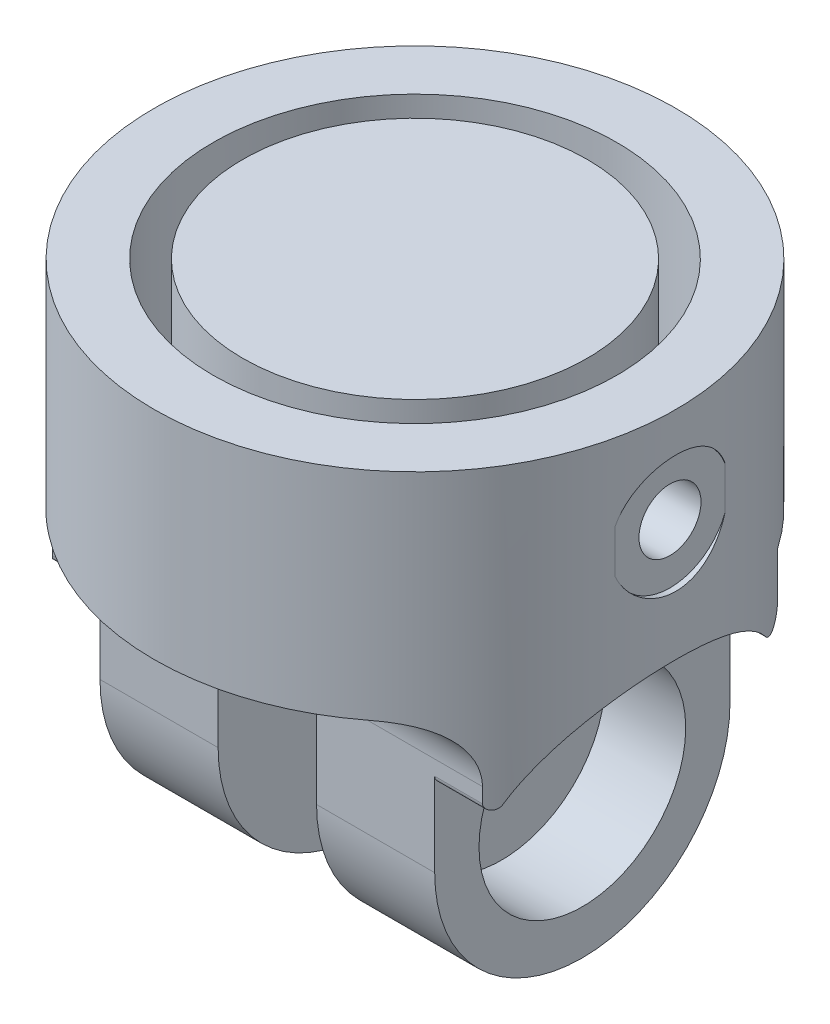
SolidWorks part; units mm, degrees
material "PLA Black"
ref_plane "Front" through (0, 0, 0) normal (0, 0, 1) x (1, 0, 0)
ref_plane "Top" through (0, 0, 0) normal (0, 1, 0) x (1, 0, 0)
ref_plane "Right" through (0, 0, 0) normal (1, 0, 0) x (0, 0, -1)
sketch "Sketch1" plane through (0, 0, 0) normal (0, 1, 0) x (1, 0, 0)
  line L0 (0, 8.75) -> (0, 10.25) construction
  circle A0 centre (0, 0) radius 10.25
  circle A1 centre (0, 0) radius 13.25
  circle A2 centre (0, 0) radius 9.5 construction
  circle A4 centre (0, 0) radius 8.75
  point P11 (0, 9.5)
  dimension "D1" = 1.5
  dimension "D2" = 3
  dimension "D3" = 19
extrude "Boss-Extrude1" add sketch "Sketch1" along normal blind 10 contours A1 A0 | A4 region at (-12.8752, 0, 0) region at (0, 0, 0)
sketch "Sketch3" plane through (0, 0, 0) normal (0, -1, 0) x (1, 0, 0)
  circle A2 centre (0, 0) radius 13.25 construction
  circle A3 centre (0, 0) radius 13.25
extrude "Boss-Extrude2" add sketch "Sketch3" along normal blind 1
sketch "Sketch4" plane through (0, -1, 0) normal (0, -1, 0) x (1, 0, 0)
  line L0 (0, 17.8908) -> (0, -17.0763) construction
  line L1 (2.5, 7.5) -> (8.5, 7.5)
  line L2 (2.5, 7.5) -> (2.5, -7.5)
  line L3 (2.5, -7.5) -> (8.5, -7.5)
  line L4 (8.5, 7.5) -> (8.5, -7.5)
  line L5 (-8.5, 7.5) -> (-8.5, -7.5)
  line L6 (-2.5, -7.5) -> (-8.5, -7.5)
  line L7 (-2.5, 7.5) -> (-2.5, -7.5)
  line L8 (-2.5, 7.5) -> (-8.5, 7.5)
  line L9 (16.8049, 0) -> (-19.8998, 0) construction
  dimension "D1" = 6
  dimension "D2" = 5
  dimension "D3" = 15
extrude "Boss-Extrude3" add sketch "Sketch4" along normal blind 16
sketch "Sketch5" plane through (8.5, 0, 0) normal (1, 0, 0) x (0, 0, -1)
  line L0 (-7.5, -17) -> (-7.5, -1) construction
  line L1 (7.5, -17) -> (7.5, -1) construction
  line L2 (7.5, -9) -> (7.5, -17.1619)
  line L3 (7.5, -17.1619) -> (-7.5, -17.1619)
  line L4 (-7.5, -17.1619) -> (-7.5, -9)
  arc A0 (-7.5, -9) -> (7.5, -9) centre (0, -9) ccw
  circle A1 centre (0, -9) radius 1.75
  dimension "D1" = 3.5
extrude "Cut-Extrude1" cut sketch "Sketch5" against normal through all both and the other way through all
sketch "Sketch6" plane through (8.5, 0, 0) normal (1, 0, 0) x (0, 0, -1)
  circle A0 centre (0, -9) radius 5.25
  dimension "D1" = 10.5
extrude "Cut-Extrude2" cut sketch "Sketch6" against normal blind 4.1
mirror "Mirror1" about plane through (0, 0, 0) normal (1, 0, 0) of "Cut-Extrude2"
ref_plane "Plane9" through (2.25, 0, 0) normal (1, 0, 0) x (0, 0, -1)
sketch "Sketch7" plane through (2.25, 0, 0) normal (1, 0, 0) x (0, 0, -1)
  line L0 (3.6, -9) -> (3.6, -1) construction
  line L1 (7.5, -1) -> (-7.5, -1) construction
  line L2 (3.5026, -8.1681) -> (1.8, -1) construction
  line L3 (3.2149, -7.38) -> (0, -1) construction
  line L4 (1.8, -0.6757) -> (1.8, -1.4422) construction
  line L5 (2.8087, -6.748) -> (-1.8, -1) construction
  line L6 (2.3875, -6.3056) -> (-3.6, -1) construction
  line L8 (0, -1.6788) -> (0, 0) construction
  line L9 (-8.4824, -9) -> (8.712, -9) construction
  line L10 (2.0173, -6.0183) -> (-5.4, -1) construction
  line L11 (-3.6, -0.3587) -> (-3.6, -1.6788) construction
  circle A0 centre (0, -9) radius 3.6 construction
  dimension "D1" = 7.2
  dimension "D2" = 34.081
  dimension "D3" = 8
ref_plane "Plane1" through (2.25, -1, -3.6) normal (0, 1, 0) x (1, 0, 0)
ref_plane "Plane2" through (2.25, -1, -1.8) normal (0, 0.9729, 0.2311) x (1, 0, 0)
ref_plane "Plane3" through (2.25, -1, 0) normal (0, 0.893, 0.45) x (1, 0, 0)
ref_plane "Plane5" through (2.25, -1, 1.8) normal (0, 0.7802, 0.6255) x (1, 0, 0)
ref_plane "Plane6" through (2.25, -1, 3.6) normal (0, 0.6632, 0.7484) x (1, 0, 0)
ref_plane "Plane7" through (2.25, -1, 5.4) normal (0, 0.5604, 0.8282) x (1, 0, 0)
sketch "Sketch8" plane through (2.25, -1, -3.6) normal (0, 1, 0) x (1, 0, 0)
  circle A0 centre (0, 0) radius 0.825
  dimension "D1" = 1.65
extrude "Cut-Extrude5" cut sketch "Sketch8" along normal blind 5.5 and the other way through all
sketch "Sketch9" plane through (2.25, -1, -1.8) normal (0, 0.9729, 0.2311) x (1, 0, 0)
  circle A0 centre (0, 0) radius 0.825
  dimension "D1" = 1.65
extrude "Cut-Extrude3" cut sketch "Sketch9" along normal blind 5.5
sketch "Sketch10" plane through (2.25, -1, 0) normal (0, 0.893, 0.45) x (1, 0, 0)
  circle A0 centre (0, 0) radius 0.825
  dimension "D1" = 1.65
sketch "Sketch11" plane through (2.25, -1, 1.8) normal (0, 0.7802, 0.6255) x (1, 0, 0)
  circle A0 centre (0, 0) radius 0.825
  dimension "D1" = 1.65
sketch "Sketch12" plane through (2.25, -1, 3.6) normal (0, 0.6632, 0.7484) x (1, 0, 0)
  circle A0 centre (0, 0) radius 0.825
  dimension "D1" = 1.65
sketch "Sketch14" plane through (2.25, -1, 5.4) normal (0, 0.5604, 0.8282) x (1, 0, 0)
  circle A0 centre (0, 0) radius 0.825
  dimension "D1" = 1.65
extrude "Cut-Extrude6" cut sketch "Sketch10" along normal blind 5.5 and the other way through all
extrude "Cut-Extrude7" cut sketch "Sketch11" along normal blind 5.5 and the other way through all contours A0
extrude "Cut-Extrude8" cut sketch "Sketch12" along normal blind 5.5 and the other way through all contours A0
extrude "Cut-Extrude9" cut sketch "Sketch14" along normal blind 5.5 and the other way through all contours A0
ref_plane "Plane8" through (13.25, 0, 0) normal (1, 0, 0) x (0, 0, -1)
hole_wizard "Tap Drill for M3 Helicoil1" positions "Sketch17" profile "Sketch18" hole size "M3x0.5" standard "DIN"
sketch "Sketch17" plane through (13.25, 0, 0) normal (1, 0, 0) x (0, 0, -1)
  line L0 (-22.2973, 5) -> (18.0703, 5) construction
  line L4 (0, 12.2732) -> (0, -5.3405) construction
  line L6 (-7.5, -9) -> (-7.5, -1) construction
  line L7 (7.5, -9) -> (7.5, -1) construction
  line L8 (13.25, 10) -> (-13.25, 10) construction
  line L9 (10.25, 0) -> (-10.25, 0) construction
  point P0 (0, 5)
sketch "Sketch18" plane through (13.25, 5, 0) normal (0, 1, 0) x (0, 0, -1)
  line L0 (0, 0) -> (0, 6.9464)
  line L1 (0, 6.9464) -> (1.575, 6)
  line L2 (1.575, 6) -> (1.575, 0)
  line L5 (1.575, 0) -> (0, 0)
  line L10 (0, 6.9464) -> (-1.575, 6) construction
  line L11 (0, -6.35) -> (0, 107.95) construction
  dimension "Hole Dia." = 3.15
  dimension "Hole Depth" = 6
  dimension "Drill Angle" = 118
sketch "Sketch20" plane through (13.25, 0, 0) normal (1, 0, 0) x (0, 0, -1)
  circle A0 centre (0, 5) radius 3
  dimension "D1" = 6
extrude "Cut-Extrude10" cut sketch "Sketch20" against normal blind 0.3
sketch "Sketch21" plane through (8.5, 0, 0) normal (1, 0, 0) x (0, 0, -1)
  line L0 (7.5, -1) -> (-7.5, -1) construction
  line L1 (7.5, -0.1252) -> (7.5, -3.188)
  line L2 (0.9244, -19.5662) -> (-4.8209, -14.7453) construction
  line L3 (0, 5.2718) -> (0, -9.2894) construction
  line L4 (0, 10) -> (0, -1) construction
  line L5 (-7.5, -0.1252) -> (-7.5, -4.7575)
  line L6 (7.5, -0.1252) -> (-7.5, -0.1252)
  line L7 (-7.5, -9) -> (-7.5, -1) construction
  line L8 (7.5, -9) -> (7.5, -1) construction
  line L9 (0, -1) -> (9.1102, -5.2607) construction
  line L10 (0, -1) -> (1.2641, -0.2702) construction
  line L11 (6.0277, -3.7401) -> (7.5, -3.188) construction
  line L12 (10.5662, -8.0756) -> (4.8209, -3.2547) construction
  line L13 (-4.8209, -14.7453) -> (4.8209, -3.2547) construction
  line L14 (10.5662, -8.0756) -> (0.9244, -19.5662) construction
  arc A0 (-6.8849, -4.9259) -> (6.0277, -3.7401) centre (0, -9) cw
  arc A1 (-6.8849, -4.9259) -> (-7.5, -4.7575) centre (-7.1694, -4.7575) cw
  arc A2 (7.5, -3.188) -> (6.0277, -3.7401) centre (6.6603, -3.188) cw
  circle A3 centre (0, -9) radius 1.75 construction
  arc A4 (-4.8209, -14.7453) -> (4.8209, -3.2547) centre (0, -9) cw construction
  dimension "D1" = 30
  dimension "D3" = 7.5
  dimension "D2" = 50
  dimension "D4" = 15
extrude "Boss-Extrude4" add sketch "Sketch21" along normal up to surface (2.423 mm away) up to face at (13.0965, 5, 0)
mirror "Mirror2" about plane through (0, 0, 0) normal (1, 0, 0) of "Boss-Extrude4", "Tap Drill for M3 Helicoil1", "Cut-Extrude10"
fillet "Fillet1" radius 3 2 edges at (-6.7115, -1, 7.5) (6.7115, -1, 7.5)
equation "\"knee_angle\"= 70"
equation "\"ankle_angle\" = 80"
equation "\"hip_angle\" = 40"
equation "\"spring_ankle_parallel_arm_diameter\"= 1.5"
equation "\"spring_ankle_parallel_arm_length\"= 13"
equation "\"spring_ankle_parallel_intern_diameter\"= 5.7"
equation "\"spring_ankle_parallel_angle\"= \"ankle_angle\""
equation "\"spring_ankle_parallel_turns\"= 3"
equation "\"spring_ankle_parallel_pitch\"= \"spring_ankle_parallel_arm_diameter\" * 1.01"
equation "\"spring_ankle_parallel_cutting_distance\"= (1-\"spring_ankle_parallel_angle\" / 360) * \"spring_ankle_parallel_pitch\""
equation "\"spring_ankle_serial_arm_diameter\"= 1.91"
equation "\"spring_ankle_serial_arm_length\"= 10"
equation "\"spring_ankle_serial_intern_diameter\"= 5.7"
equation "\"spring_ankle_serial_angle\"= \"90\""
equation "\"spring_ankle_serial_turns\"= 3"
equation "\"spring_ankle_serial_pitch\"= \"spring_ankle_serial_arm_diameter\" * 1.01"
equation "\"spring_ankle_serial_cutting_distance\"= (1-\"spring_ankle_serial_angle\" / 360) * \"spring_ankle_serial_pitch\""
equation "\"spring_knee_parallel_arm_diameter\"= 1.5"
equation "\"spring_knee_parallel_arm_length\"= 13"
equation "\"spring_knee_parallel_intern_diameter\"= 5.7"
equation "\"spring_knee_parallel_angle\"= -\"knee_angle\" + 90"
equation "\"spring_knee_parallel_turns\"= 3"
equation "\"spring_knee_parallel_pitch\"= \"spring_knee_parallel_arm_diameter\" * 1.01"
equation "\"spring_knee_parallel_cutting_distance\"= (1-(\"spring_knee_parallel_angle\") / 360) * \"spring_knee_parallel_pitch\""
equation "\"spring_knee_serial_arm_diameter\"= 1.91"
equation "\"spring_knee_serial_arm_length\"= 10"
equation "\"spring_knee_serial_intern_diameter\"= 5.7"
equation "\"spring_knee_serial_angle\"= \"90\""
equation "\"spring_knee_serial_turns\"= 3"
equation "\"spring_knee_serial_pitch\"= \"spring_knee_serial_arm_diameter\" * 1.01"
equation "\"spring_knee_serial_cutting_distance\"= (1-\"spring_knee_serial_angle\" / 360) * \"spring_knee_serial_pitch\""
equation "\"spring_ankle_parallel_nominal_diameter\"= \"spring_ankle_parallel_arm_diameter\" + \"spring_ankle_parallel_intern_diameter\""
equation "\"spring_ankle_serial_nominal_diameter\"= \"spring_ankle_serial_arm_diameter\" + \"spring_ankle_serial_intern_diameter\""
equation "\"spring_knee_parallel_nominal_diameter\"= \"spring_knee_parallel_arm_diameter\" + \"spring_knee_parallel_intern_diameter\""
equation "\"spring_knee_serial_nominal_diameter\"= \"spring_knee_serial_arm_diameter\" + \"spring_knee_serial_intern_diameter\""
equation "\"D1@Sketch7\"=\"spring_ankle_parallel_nominal_diameter\""
equation "\"D1@Sketch8\"=\"spring_ankle_parallel_arm_diameter\"*1.1"
equation "\"D1@Sketch9\"=\"spring_ankle_parallel_arm_diameter\"*1.1"
equation "\"D1@Sketch10\"=\"spring_ankle_parallel_arm_diameter\"*1.1"
equation "\"D1@Sketch11\"=\"spring_ankle_parallel_arm_diameter\"*1.1"
equation "\"D1@Sketch12\"=\"spring_ankle_parallel_arm_diameter\"*1.1"
equation "\"D1@Sketch14\"=\"spring_ankle_parallel_arm_diameter\"*1.1"
equation "\"D1@Cut-Extrude3\"=\"spring_ankle_parallel_arm_length\"-\"axis_structure_distance\""
equation "\"axis_structure_distance\"= 7.5"
equation "\"D1@Cut-Extrude5\"=\"spring_ankle_parallel_arm_length\"-\"axis_structure_distance\""
equation "\"D1@Cut-Extrude6\"=\"spring_ankle_parallel_arm_length\"-\"axis_structure_distance\""
equation "\"D1@Cut-Extrude7\"=\"spring_ankle_parallel_arm_length\"-\"axis_structure_distance\""
equation "\"D1@Cut-Extrude8\"=\"spring_ankle_parallel_arm_length\"-\"axis_structure_distance\""
equation "\"D1@Cut-Extrude9\"=\"spring_ankle_parallel_arm_length\"-\"axis_structure_distance\""
equation "\"D1@Boss-Extrude3\"=\"axis_structure_distance\"*2"
equation "\"ankle_angle_max\" = 120"
equation "\"ankle_angle_min\" = 50"
equation "\"knee_angle_max\" = 120"
equation "\"knee_angle_min\" = 0"
equation "\"hip_angle_max\" = 90"
equation "\"hip_angle_min\" = -60"
equation "\"D1@Sketch21\"=\"ankle_angle_max\"-90"
equation "\"D2@Sketch21\"=\"ankle_angle_min\""
equation "\"D1@Plane9\"=(\"spring_ankle_parallel_arm_diameter\"*\"spring_ankle_parallel_turns\")/2"
